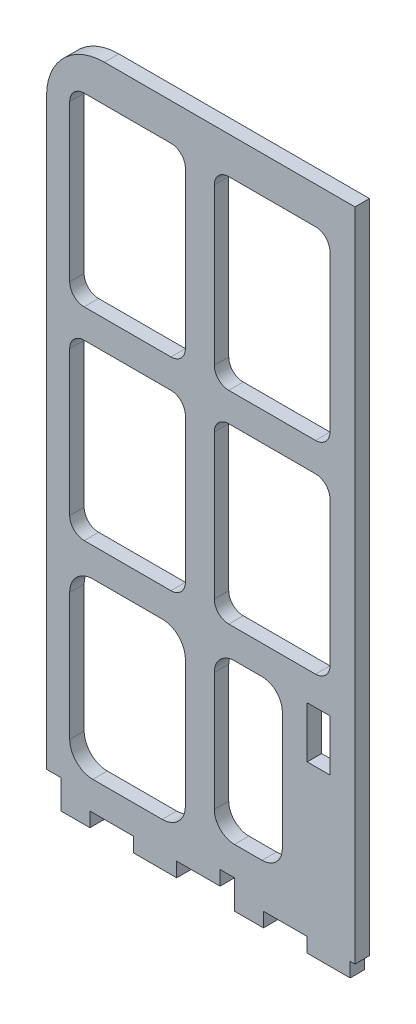
SolidWorks part; units mm, degrees
material "Balsa"
ref_plane "Front Plane" through (0, 0, 0) normal (0, 0, 1) x (1, 0, 0)
ref_plane "Top Plane" through (0, 0, 0) normal (0, 1, 0) x (1, 0, 0)
ref_plane "Right Plane" through (0, 0, 0) normal (1, 0, 0) x (0, 0, -1)
sketch "Sketch1" plane through (0, 0, 0) normal (0, 0, 1) x (1, 0, 0)
  line L1 (135.4577, 0) -> (135.4577, 287.9852)
  line L2 (135.4577, 287.9852) -> (25.4, 287.9852)
  line L4 (0, 0) -> (0, -6.35)
  line L6 (0, 0) -> (0, -6.35)
  line L7 (0, -6.35) -> (19.05, -6.35)
  line L8 (19.05, 0) -> (19.05, -6.35)
  line L10 (38.1, 0) -> (38.1, -6.35)
  line L11 (38.1, -6.35) -> (57.15, -6.35)
  line L12 (57.15, 0) -> (57.15, -6.35)
  line L14 (76.2, 0) -> (76.2, -6.35)
  line L15 (76.2, -6.35) -> (95.25, -6.35)
  line L16 (95.25, 0) -> (95.25, -6.35)
  line L18 (114.3, 0) -> (114.3, -6.35)
  line L19 (114.3, -6.35) -> (133.35, -6.35)
  line L20 (133.35, 0) -> (133.35, -6.35)
  line L25 (19.05, 0) -> (38.1, 0)
  line L26 (57.15, 0) -> (76.2, 0)
  line L27 (95.25, 0) -> (114.3, 0)
  line L28 (133.35, 0) -> (135.4577, 0)
  line L30 (0, 262.5852) -> (0, 0)
  line L31 (25.4, 287.9852) -> (135.4577, 287.9852)
  line L32 (19.05, 0) -> (38.1, 0)
  line L33 (38.1, -6.35) -> (57.15, -6.35)
  line L34 (57.15, 0) -> (76.2, 0)
  arc A0 (25.4, 287.9852) -> (0, 262.5852) centre (25.4, 262.5852) ccw
  point P8 (0, 287.9852)
  point P11 (135.4577, 287.9852)
  dimension "D4" = 6.35
  dimension "D5" = 19.05
  dimension "D1" = 135.4577
  dimension "D2" = 287.9852
  dimension "D3" = 135.4577
  dimension "D6" = 6.35
  dimension "D7" = 19.05
  dimension "D8" = 19.05
  dimension "D9" = 19.05
  dimension "D10" = 19.05
  dimension "D11" = 6.35
  dimension "D12" = 19.05
  dimension "D13" = 19.05
  dimension "D14" = 6.35
  dimension "D15" = 6.35
  dimension "D16" = 0
  dimension "D17" = 262.5852
  dimension "D21" = 6.35
  dimension "D22" = 6.35
  dimension "D23" = 6.35
extrude "Boss-Extrude1" add sketch "Sketch1" along normal blind 6.35 contours L2 A0 L30 L4 L7 L8 L25 L10 L11 L12 L26 L14 L15 L16 L27 L18 L19 L20 L1 region at (67.9342, 141.6966, 0)
sketch "Sketch2" plane through (0, 0, 6.35) normal (0, 0, 1) x (1, 0, 0)
  line L38 (73.66, 22.86) -> (73.66, 78.74)
  line L39 (20.32, 12.7) -> (50.8, 12.7)
  line L40 (73.66, 196.85) -> (73.66, 265.43)
  line L41 (80.01, 190.5) -> (118.11, 190.5)
  line L42 (124.46, 196.85) -> (124.46, 265.43)
  line L43 (80.01, 271.78) -> (118.11, 271.78)
  line L45 (10.16, 196.85) -> (10.16, 265.43)
  line L46 (16.51, 190.5) -> (54.61, 190.5)
  line L47 (60.96, 196.85) -> (60.96, 265.43)
  line L48 (16.51, 271.78) -> (54.61, 271.78)
  line L49 (73.66, 107.95) -> (73.66, 171.45)
  line L50 (80.01, 101.6) -> (118.11, 101.6)
  line L51 (124.46, 107.95) -> (124.46, 171.45)
  line L52 (80.01, 177.8) -> (118.11, 177.8)
  line L53 (10.16, 107.95) -> (10.16, 171.45)
  line L54 (16.51, 101.6) -> (54.61, 101.6)
  line L55 (60.96, 107.95) -> (60.96, 171.45)
  line L56 (16.51, 177.8) -> (54.61, 177.8)
  line L68 (10.16, 22.86) -> (10.16, 78.74)
  line L69 (20.32, 88.9) -> (50.8, 88.9)
  line L70 (60.96, 22.86) -> (60.96, 78.74)
  line L71 (83.82, 12.7) -> (114.3, 12.7)
  line L72 (124.46, 22.86) -> (124.46, 78.74)
  line L73 (83.82, 88.9) -> (114.3, 88.9)
  line L104 (19.05, -38.1) -> (44.45, -38.1) [skipped]
  line L105 (137.16, 19.05) -> (137.16, 82.55) [skipped]
  line L106 (146.05, 12.7) -> (171.45, 12.7) [skipped]
  line L107 (187.96, 19.05) -> (187.96, 82.55) [skipped]
  line L108 (146.05, 88.9) -> (171.45, 88.9) [skipped]
  line L109 (137.16, -44.45) -> (137.16, 19.05) [skipped]
  line L110 (146.05, -50.8) -> (171.45, -50.8) [skipped]
  line L111 (187.96, -44.45) -> (187.96, 19.05) [skipped]
  line L112 (146.05, 25.4) -> (171.45, 25.4) [skipped]
  line L113 (137.16, -103.373) -> (137.16, -49.027) [skipped]
  line L114 (150.627, -114.3) -> (166.873, -114.3) [skipped]
  line L115 (187.96, -103.373) -> (187.96, -49.027) [skipped]
  line L116 (150.627, -38.1) -> (166.873, -38.1) [skipped]
  line L117 (73.66, -97.4702) -> (73.66, -54.9298) [skipped]
  line L118 (124.46, -97.4702) -> (124.46, -54.9298) [skipped]
  line L119 (93.0298, -114.3) -> (97.4702, -114.3) [skipped]
  line L120 (93.0298, -38.1) -> (97.4702, -38.1) [skipped]
  line L121 (10.16, -105.3232) -> (10.16, -47.0768) [skipped]
  line L122 (37.2067, -114.3) -> (48.1202, -114.3) [skipped]
  line L123 (60.96, -105.3232) -> (60.96, -58.7589) [skipped]
  line L124 (19.05, 25.4) -> (44.45, 25.4) [skipped]
  line L125 (60.96, -50.8) -> (60.96, 25.4) [skipped]
  line L126 (19.05, -50.8) -> (44.45, -50.8) [skipped]
  line L127 (10.16, -50.8) -> (10.16, 25.4) [skipped]
  line L128 (124.46, -69.3053) -> (124.46, 6.8947) [skipped]
  line L129 (73.66, -50.8) -> (73.66, 25.4) [skipped]
  line L130 (94.7053, 25.4) -> (103.4599, 25.4) [skipped]
  line L131 (94.7053, -50.8) -> (103.4599, -50.8) [skipped]
  arc A24 (73.66, 78.74) -> (83.82, 88.9) centre (83.82, 78.74) cw
  arc A25 (124.46, 78.74) -> (114.3, 88.9) centre (114.3, 78.74) ccw
  arc A26 (114.3, 12.7) -> (124.46, 22.86) centre (114.3, 22.86) ccw
  arc A27 (73.66, 22.86) -> (83.82, 12.7) centre (83.82, 22.86) ccw
  arc A28 (50.8, 12.7) -> (60.96, 22.86) centre (50.8, 22.86) ccw
  arc A29 (50.8, 88.9) -> (60.96, 78.74) centre (50.8, 78.74) cw
  arc A30 (10.16, 78.74) -> (20.32, 88.9) centre (20.32, 78.74) cw
  arc A31 (20.32, 12.7) -> (10.16, 22.86) centre (20.32, 22.86) cw
  arc A57 (10.16, 196.85) -> (16.51, 190.5) centre (16.51, 196.85) ccw
  arc A58 (10.16, 265.43) -> (16.51, 271.78) centre (16.51, 265.43) cw
  arc A59 (60.96, 265.43) -> (54.61, 271.78) centre (54.61, 265.43) ccw
  arc A60 (54.61, 190.5) -> (60.96, 196.85) centre (54.61, 196.85) ccw
  arc A61 (73.66, 196.85) -> (80.01, 190.5) centre (80.01, 196.85) ccw
  arc A62 (73.66, 265.43) -> (80.01, 271.78) centre (80.01, 265.43) cw
  arc A63 (124.46, 265.43) -> (118.11, 271.78) centre (118.11, 265.43) ccw
  arc A64 (118.11, 190.5) -> (124.46, 196.85) centre (118.11, 196.85) ccw
  arc A65 (10.16, 107.95) -> (16.51, 101.6) centre (16.51, 107.95) ccw
  arc A66 (10.16, 171.45) -> (16.51, 177.8) centre (16.51, 171.45) cw
  arc A67 (60.96, 171.45) -> (54.61, 177.8) centre (54.61, 171.45) ccw
  arc A68 (54.61, 101.6) -> (60.96, 107.95) centre (54.61, 107.95) ccw
  arc A69 (73.66, 107.95) -> (80.01, 101.6) centre (80.01, 107.95) ccw
  arc A70 (73.66, 171.45) -> (80.01, 177.8) centre (80.01, 171.45) cw
  arc A71 (124.46, 171.45) -> (118.11, 177.8) centre (118.11, 171.45) ccw
  arc A72 (118.11, 101.6) -> (124.46, 107.95) centre (118.11, 107.95) ccw
  point P88 (60.96, 12.7)
  point P93 (10.16, 88.9)
  point P96 (10.16, 12.7)
  dimension "D7" = 81.28
  dimension "D12" = 76.2
  dimension "D11" = 50.8
  dimension "D1" = 76.2
  dimension "D2" = 50.8
  dimension "D3" = 3
  dimension "D4" = 3
  dimension "D5" = 10.16
  dimension "D6" = 12.7
  dimension "D8" = 12.7
  dimension "D9" = 81.28
  dimension "D10" = 50.8
  dimension "D13" = 76.2
  dimension "D14" = 50.8
  dimension "D15" = 50.8
  dimension "D16" = 12.7
  dimension "D17" = 12.7
  dimension "D18" = 0
  dimension "D19" = 0
  dimension "D20" = 12.7
  dimension "D21" = 12.7
  dimension "D22" = 12.7
  dimension "D23" = 12.7
extrude "Cut-Extrude1" cut sketch "Sketch2" against normal through all
sketch "Sketch3" plane through (0, 0, 6.35) normal (0, 0, 1) x (1, 0, 0)
  line L1 (0, -6.35) -> (6.35, -6.35)
  line L2 (0, -6.35) -> (0, 6.35)
  line L3 (0, 6.35) -> (6.35, 6.35)
  line L4 (6.35, -6.35) -> (6.35, 6.35)
  line L5 (76.2, -6.35) -> (82.55, -6.35)
  line L6 (76.2, -6.35) -> (76.2, 6.35)
  line L7 (76.2, 6.35) -> (82.55, 6.35)
  line L8 (82.55, -6.35) -> (82.55, 6.35)
  dimension "D1" = 6.35
  dimension "D2" = 12.7
  dimension "D3" = 6.35
  dimension "D4" = 12.7
extrude "Cut-Extrude2" cut sketch "Sketch3" against normal through all
sketch "Sketch4" plane through (0, 0, 6.35) normal (0, 0, 1) x (1, 0, 0)
  line L5 (69.1558, 89.874) -> (128.0503, 89.874)
  line L6 (69.1558, 89.874) -> (69.1558, 9.4409)
  line L7 (69.1558, 9.4409) -> (128.0503, 9.4409)
  line L8 (128.0503, 89.874) -> (128.0503, 9.4409)
  dimension "D1" = 80.433
extrude "Boss-Extrude3" add sketch "Sketch4" against normal up to surface (6.35 mm away) from surface contours L8 L7 L6 L5 up to face at (99.06, 50.8, 0) starting at face at (66.7676, 35.5833, 6.35)
ref_plane "Plane1" through (50.8, 88.9, 0) normal (-1, 0, 0) x (0, 0, 1)
sketch "Sketch6" plane through (0, 0, 0) normal (0, 0, -1) x (-1, 0, 0)
  line L1 (-124.46, 88.9) -> (-114.46, 88.9)
  line L2 (-124.46, 88.9) -> (-124.46, 66.4)
  line L3 (-124.46, 66.4) -> (-114.46, 66.4)
  line L4 (-114.46, 88.9) -> (-114.46, 66.4)
  dimension "D1" = 10
  dimension "D2" = 22.5
extrude "Cut-Extrude3" cut sketch "Sketch6" against normal through all
sketch "Sketch7" plane through (0, 0, 6.35) normal (0, 0, 1) x (1, 0, 0)
  line L0 (50.8, 88.9) -> (20.32, 88.9) construction
  line L1 (82.55, 88.9) -> (94.648, 88.9)
  line L2 (73.66, 80.01) -> (73.66, 27.94)
  line L3 (82.55, 19.05) -> (94.648, 19.05)
  line L4 (103.538, 80.01) -> (103.538, 27.94)
  line L5 (73.66, 171.45) -> (73.66, 107.95) construction
  line L6 (82.55, -6.35) -> (95.25, -6.35) construction
  line L7 (114.46, 66.4) -> (114.46, 88.9) construction
  arc A0 (73.66, 27.94) -> (82.55, 19.05) centre (82.55, 27.94) ccw
  arc A1 (94.648, 19.05) -> (103.538, 27.94) centre (94.648, 27.94) ccw
  arc A2 (94.648, 88.9) -> (103.538, 80.01) centre (94.648, 80.01) cw
  arc A3 (82.55, 88.9) -> (73.66, 80.01) centre (82.55, 80.01) ccw
  dimension "D2" = 8.89
  dimension "D1" = 10.922
  dimension "D3" = 25.4
extrude "Cut-Extrude4" cut sketch "Sketch7" against normal up to surface (6.35 mm away) up to face at (119.46, 77.65, 0)
